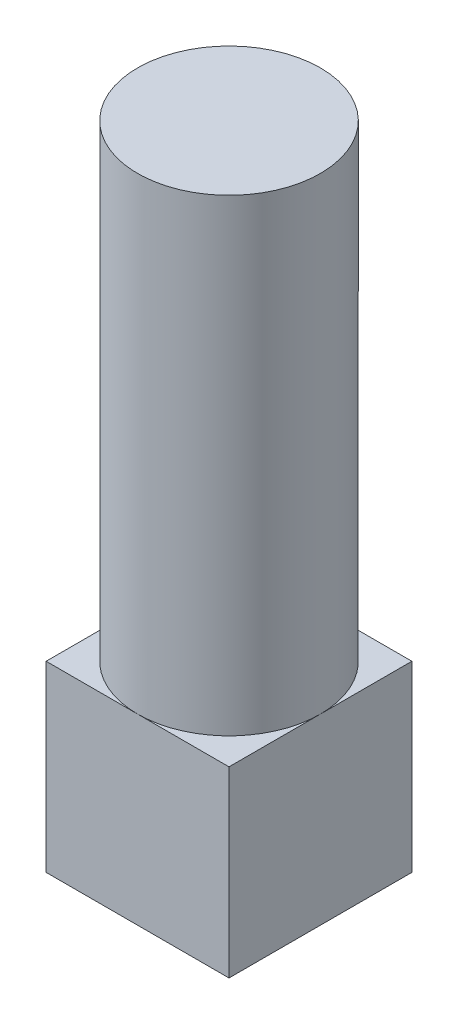
SolidWorks part; units mm, degrees
ref_plane "Front Plane" through (0, 0, 0) normal (0, 0, 1) x (1, 0, 0)
ref_plane "Top Plane" through (0, 0, 0) normal (0, 1, 0) x (1, 0, 0)
ref_plane "Right Plane" through (0, 0, 0) normal (1, 0, 0) x (0, 0, -1)
sketch "Sketch1" plane through (0, 0, 0) normal (0, 1, 0) x (1, 0, 0)
  line L1 (-3.175, 3.175) -> (3.175, 3.175)
  line L2 (-3.175, 3.175) -> (-3.175, -3.175)
  line L3 (-3.175, -3.175) -> (3.175, -3.175)
  line L4 (3.175, 3.175) -> (3.175, -3.175)
  line L5 (-3.175, 3.175) -> (3.175, -3.175) construction
  line L6 (-3.175, -3.175) -> (3.175, 3.175) construction
  point P0 (0, 0)
  dimension "D1" = 6.35
extrude "Boss-Extrude1" add sketch "Sketch1" along normal blind 6.35
sketch "Sketch2" plane through (0, 0, 0) normal (0, -1, 0) x (1, 0, 0)
  line L0 (3.175, 3.175) -> (3.175, -3.175) construction
  circle A0 centre (0, 0) radius 3.175
extrude "Boss-Extrude2" add sketch "Sketch2" against normal blind 22.606
